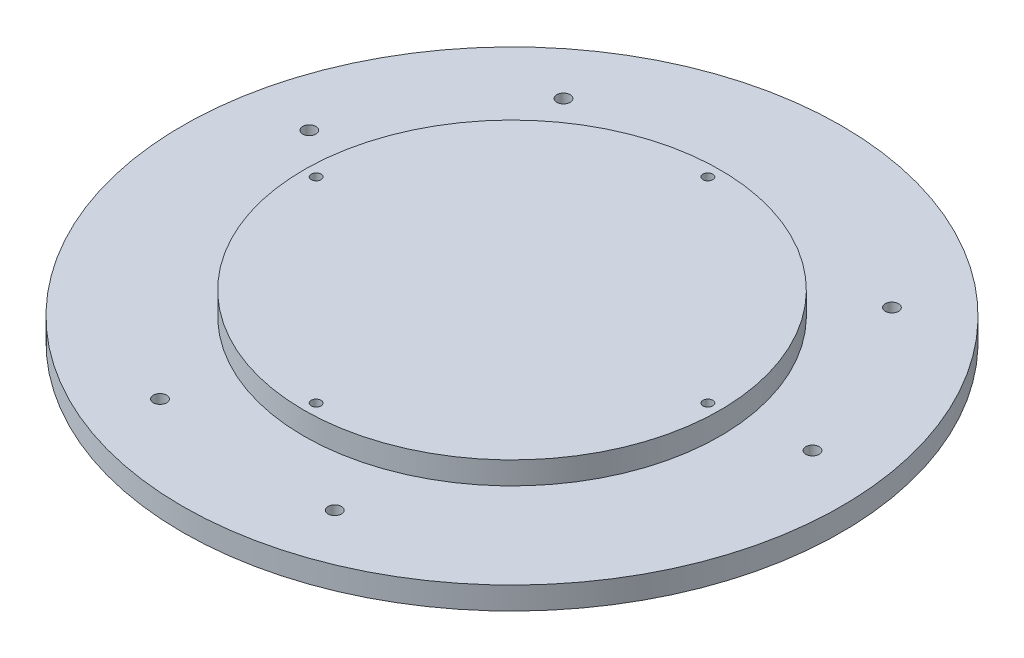
SolidWorks part; units mm, degrees
ref_plane "Plan de face" through (0, 0, 0) normal (0, 0, 1) x (1, 0, 0)
ref_plane "Plan de dessus" through (0, 0, 0) normal (0, 1, 0) x (1, 0, 0)
ref_plane "Plan de droite" through (0, 0, 0) normal (1, 0, 0) x (0, 0, -1)
sketch "Esquisse1" plane through (0, 0, 0) normal (0, 1, 0) x (1, 0, 0)
  circle A0 centre (0, 0) radius 84.1225
  dimension "D1" = 168.245
extrude "Boss.-Extru.1" add sketch "Esquisse1" against normal blind 5.75
sketch "Esquisse2" plane through (0, 0, 0) normal (0, 1, 0) x (1, 0, 0)
  circle A0 centre (0, 0) radius 53.13
  dimension "D1" = 106.26
extrude "Boss.-Extru.2" add sketch "Esquisse2" along normal blind 5.75
sketch "Esquisse4" plane through (0, -5.75, 0) normal (0, 1, 0) x (1, 0, 0)
  circle A0 centre (0, 0) radius 50
  circle A1 centre (0, 50) radius 1.5
  circle A2 centre (50, 0) radius 1.5
  circle A3 centre (0, -50) radius 1.5
  circle A4 centre (-50, 0) radius 1.5
  dimension "D1" = 100
  dimension "D2" = 3
hole_wizard "Trou taraudé M31" positions "Esquisse3D1" profile "Esquisse5" tap size "M3" standard "Iso"
sketch3d "Esquisse3D1"
  point P0 (0, -5.75, -50)
  point P3 (-50, -5.75, 0)
  point P6 (0, -5.75, 50)
  point P9 (50, -5.75, 0)
sketch "Esquisse5" plane through (0, -5.75, -50) normal (1, 0, 0) x (0, 0, -1)
  line L0 (0, 0) -> (0, 13.2511)
  line L1 (0, 13.2511) -> (1.25, 12.5)
  line L2 (1.25, 12.5) -> (1.25, 0)
  line L5 (1.25, 0) -> (0, 0)
  line L10 (0, 13.2511) -> (-1.25, 12.5) construction
  line L11 (0, -6.35) -> (0, 107.95) construction
  dimension "Diamètre du trou pour taraudage" = 2.5
  dimension "Profondeur du trou pour taraudage" = 12.5
  dimension "Angle de pointe" = 118
sketch "Esquisse6" plane through (0, -5.75, 0) normal (0, -1, 0) x (-1, 0, 0)
  line L0 (-68.0832, 8.6129) -> (0, 0) construction
  line L3 (-57.691, -37.1651) -> (0, 0) construction
  line L4 (-46.6184, 50.3609) -> (0, 0) construction
  line L5 (-84.1225, 0) -> (-68.6258, 0) construction
  line L6 (66.923, 15.1923) -> (0, 0) construction
  line L7 (41.5006, 54.6553) -> (0, 0) construction
  line L8 (-3.3404, 68.5444) -> (0, 0) construction
  line L9 (-20.3046, -65.5532) -> (0, 0) construction
  line L10 (26.5826, -63.2682) -> (0, 0) construction
  line L11 (61.0314, -31.3793) -> (0, 0) construction
  circle A0 centre (0, 0) radius 68.6258 construction
  circle A3 centre (-57.691, -37.1651) radius 1.5
  circle A4 centre (-68.0832, 8.6129) radius 1.5
  circle A5 centre (-46.6184, 50.3609) radius 1.5
  circle A7 centre (-3.3404, 68.5444) radius 1.5
  circle A8 centre (41.5006, 54.6553) radius 1.5
  circle A9 centre (66.923, 15.1923) radius 1.5
  circle A10 centre (61.0314, -31.3793) radius 1.5
  circle A11 centre (26.5826, -63.2682) radius 1.5
  circle A12 centre (-20.3046, -65.5532) radius 1.5
  circle A13 centre (0, 0) radius 84.1225 construction
  point P11 (-68.0832, 8.6129)
  point P31 (0, 0)
  dimension "D1" = 3
  dimension "D4" = 137.2516
  dimension "D2" = 40
  dimension "D3" = 40
  dimension "D6" = 8.63
  dimension "D5" = 3
hole_wizard "Chambrage pour vis à tête hexagonale M31" positions "Esquisse3D2" profile "Esquisse7" counterbore size "M3" standard "Iso" end condition through all
sketch3d "Esquisse3D2"
  point P0 (-26.5826, -5.75, 63.2682)
  point P3 (20.3046, -5.75, 65.5532)
  point P9 (68.0832, -5.75, -8.6129)
  point P12 (46.6184, -5.75, -50.3609)
  point P18 (-41.5006, -5.75, -54.6553)
  point P21 (-66.923, -5.75, -15.1923)
sketch "Esquisse7" plane through (-26.5826, -5.75, 63.2682) normal (1, 0, 0) x (0, 0, -1)
  line L0 (0, 0) -> (0, 11.5)
  line L1 (0, 11.5) -> (1.7, 11.5)
  line L3 (1.7, 11.5) -> (1.7, 2)
  line L4 (4.6755, 2) -> (1.7, 2)
  line L5 (4.6755, 2) -> (4.6755, 0.025)
  line L6 (4.6755, 0.025) -> (4.7005, 0)
  line L7 (4.7005, 0) -> (0, 0)
  line L8 (-4.6755, 0.025) -> (-4.7005, 0) construction
  line L11 (0, -6.35) -> (0, 107.95) construction
  dimension "Diamètre du perçage jusqu'au prochain" = 3.4
  dimension "Profondeur du perçage jusqu'au prochain" = 11.5
  dimension "Diamètre du chambrage" = 9.351
  dimension "Profondeur du chambrage" = 2
  dimension "Diamètre du fraisage entrant" = 9.401
  dimension "Angle du fraisage entrant" = 90
